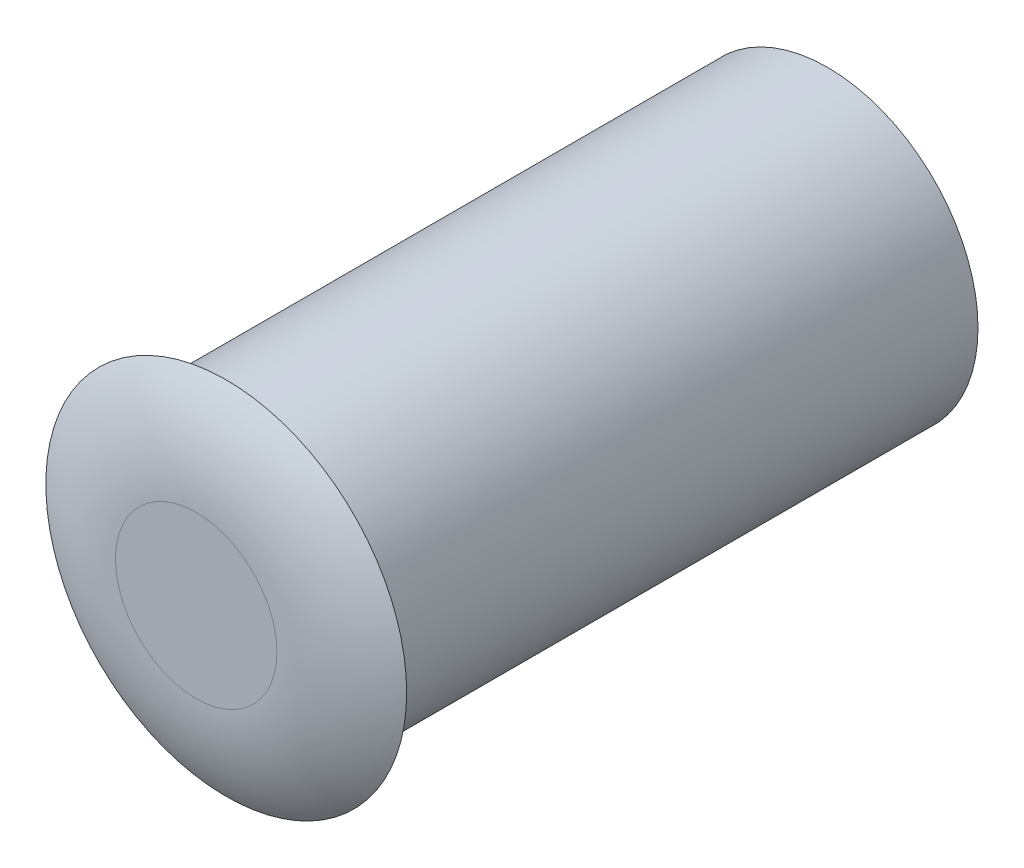
SolidWorks part; units mm, degrees
ref_plane "Front Plane" through (0, 0, 0) normal (0, 0, 1) x (1, 0, 0)
ref_plane "Top Plane" through (0, 0, 0) normal (0, 1, 0) x (1, 0, 0)
ref_plane "Right Plane" through (0, 0, 0) normal (1, 0, 0) x (0, 0, -1)
sketch "Sketch1" plane through (0, 0, 0) normal (0, 0, 1) x (1, 0, 0)
  circle A0 centre (0, 0) radius 5
  circle A1 centre (0, 0) radius 6
extrude "Boss-Extrude2" add sketch "Sketch1" against normal blind 20 contours A0
extrude "Boss-Extrude3" add sketch "Sketch1<4>" along normal blind 1 separate body contours A1
sketch "Sketch1<4>" plane through (0, 0, 0) normal (0, 0, 1) x (1, 0, 0) same geometry as "Sketch1"
fillet "Fillet1" radius 6 1 edges at (6, 0, 1)
